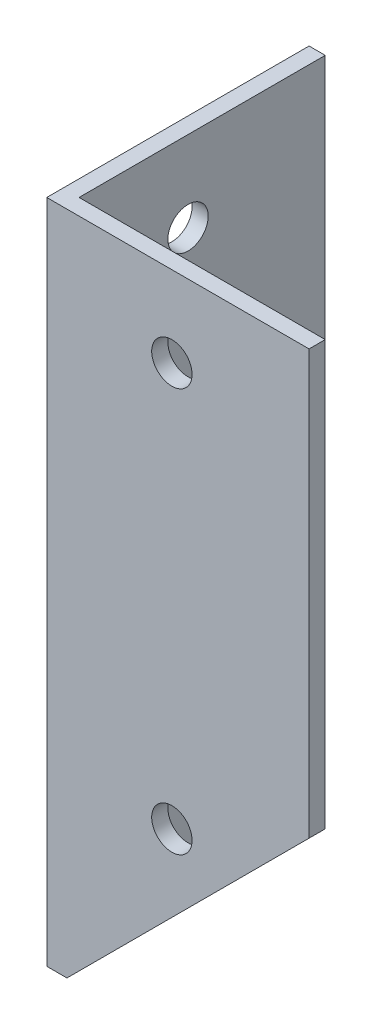
SolidWorks part; units mm, degrees
ref_plane "Спереди" through (0, 0, 0) normal (0, 0, 1) x (1, 0, 0)
ref_plane "Сверху" through (0, 0, 0) normal (0, 1, 0) x (1, 0, 0)
ref_plane "Справа" through (0, 0, 0) normal (1, 0, 0) x (0, 0, -1)
sketch "Эскиз1" plane through (0, 0, 0) normal (0, 1, 0) x (1, 0, 0)
  line L0 (0, 0) -> (65, 0)
  line L1 (0, 0) -> (0, 65)
extrude "Вытянуть-Тонкостенный1" add sketch "Эскиз1" along normal blind 165 thin thin type one direction wall 4
sketch "Эскиз2" plane through (0, 0, 0) normal (0, 0, 1) x (1, 0, 0)
  circle A0 centre (31, 145) radius 5
  circle A1 centre (31, 45) radius 5
  dimension "D1" = 2
extrude "Вырез-Вытянуть1" cut sketch "Эскиз2" against normal blind 10
sketch "Эскиз3" plane through (0, 0, 0) normal (-1, 0, 0) x (0, 0, 1)
  circle A0 centre (-31, 145) radius 5
  circle A1 centre (-31, 45) radius 5
  circle A2 centre (-15, 10) radius 5
  circle A3 centre (-45, 10) radius 5
  dimension "D1" = 2
  dimension "D2" = 2
extrude "Вырез-Вытянуть2" cut sketch "Эскиз3" against normal blind 10
sketch "Эскиз4" plane through (0, 0, 0) normal (0, 0, 1) x (1, 0, 0)
  line L0 (5, 0) -> (65, 60)
  line L1 (65, 0) -> (0, 0) construction
  line L2 (65, 165) -> (65, 0) construction
  line L3 (65, 60) -> (65, 0)
  line L4 (65, 0) -> (5, 0)
extrude "Вырез-Вытянуть3" cut sketch "Эскиз4" against normal through all
